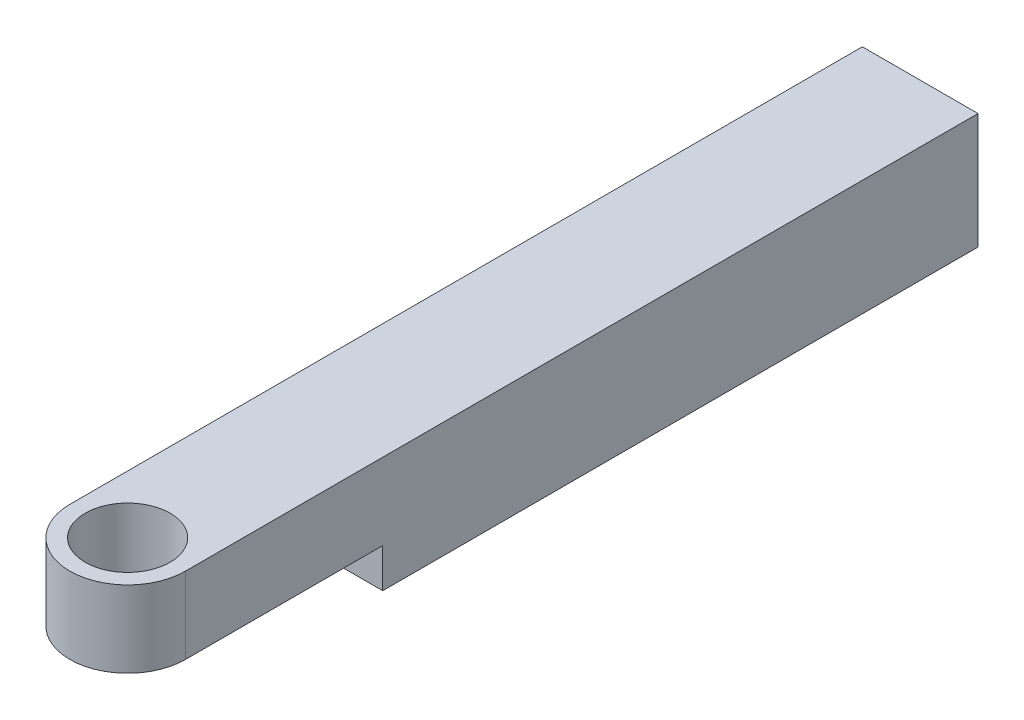
SolidWorks part; units mm, degrees
material "ABS"
ref_plane "Front Plane" through (0, 0, 0) normal (0, 0, 1) x (1, 0, 0)
ref_plane "Top Plane" through (0, 0, 0) normal (0, 1, 0) x (1, 0, 0)
ref_plane "Right Plane" through (0, 0, 0) normal (1, 0, 0) x (0, 0, -1)
sketch "Sketch1" plane through (0, 0, 0) normal (0, 0, 1) x (1, 0, 0)
  line L1 (0, 0) -> (-6.8, 0)
  line L2 (0, 0) -> (0, 6.8)
  line L3 (0, 6.8) -> (-6.8, 6.8)
  line L4 (-6.8, 0) -> (-6.8, 6.8)
  circle A0 centre (-3.4, 3.4) radius 1.75
  dimension "D3" = 3.5
  dimension "D4" = 3.4
  dimension "D5" = 3.4
  dimension "D1" = 6.8
  dimension "D2" = 6.8
extrude "Boss-Extrude1" add sketch "Sketch1" along normal blind 50
sketch "Sketch2" plane through (0, 0, 0) normal (0, 0, -1) x (-1, 0, 0)
  line L1 (6.5754, 3.4) -> (4.9877, 6.15)
  line L2 (4.9877, 6.15) -> (1.8123, 6.15)
  line L3 (1.8123, 6.15) -> (0.2246, 3.4)
  line L4 (0.2246, 3.4) -> (1.8123, 0.65)
  line L5 (1.8123, 0.65) -> (4.9877, 0.65)
  line L6 (4.9877, 0.65) -> (6.5754, 3.4)
  line L7 (0, 0) -> (0, 6.8) construction
  circle A0 centre (3.4, 3.4) radius 2.75 construction
  dimension "D1" = 5.5
  dimension "D2" = 3.4
extrude "Cut-Extrude1" cut sketch "Sketch2" against normal blind 20
sketch "Sketch5" plane through (0, 0, 50) normal (0, 0, 1) x (1, 0, 0)
  line L1 (0, 6.8) -> (-6.8, 6.8)
  line L2 (0, 6.8) -> (0, 0)
  line L3 (0, 0) -> (-6.8, 0)
  line L4 (-6.8, 6.8) -> (-6.8, 0)
  dimension "D1" = 6.8
  dimension "D2" = 6.8
extrude "Boss-Extrude2" add sketch "Sketch5" against normal blind 7
sketch "Sketch3" plane through (0, 0, 50) normal (0, 0, 1) x (1, 0, 0)
  line L6 (-6.8, 6.8) -> (-6.8, 0) construction
  line L7 (0, 0) -> (-6.8, 0)
  line L8 (0, 0) -> (0, 2.3)
  line L9 (0, 2.3) -> (-6.8, 2.3)
  line L10 (-6.8, 0) -> (-6.8, 2.3)
  line L11 (0, 6.8) -> (-6.8, 6.8) construction
  dimension "D1" = 4.5
extrude "Cut-Extrude2" cut sketch "Sketch3" against normal blind 15
sketch "Sketch4" plane through (0, 2.3, 0) normal (0, -1, 0) x (1, 0, 0)
  line L0 (0, 35) -> (0, 50) construction
  line L1 (0, 50) -> (-6.8, 50) construction
  circle A0 centre (-3.4, 46.6) radius 2.5
  dimension "D1" = 5
  dimension "D2" = 3.4
  dimension "D3" = 3.4
extrude "Cut-Extrude3" cut sketch "Sketch4" against normal blind 20
fillet "Fillet3" 2 edges at (-6.8, 4.55, 50) (0, 4.55, 50) type full round first side face at (-6.8, 3.0333, 28.3333) second side face at (0, 3.0333, 28.3333) middle face at (-3.4, 4.55, 50)
